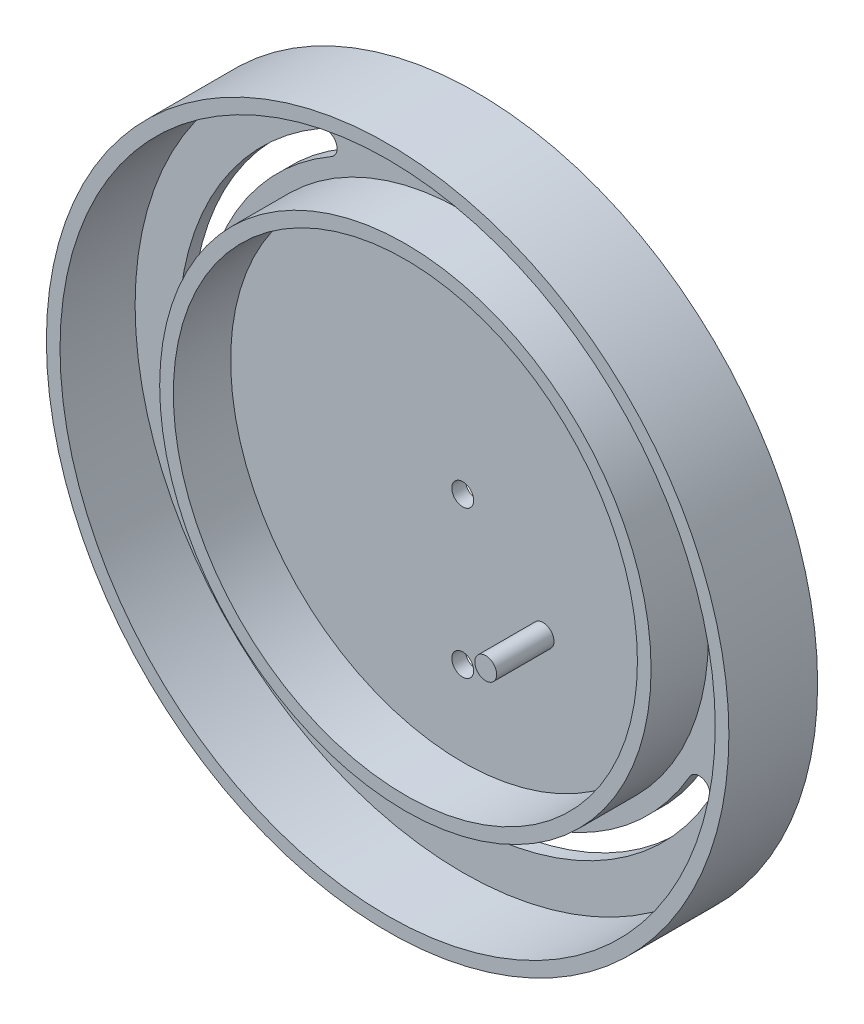
SolidWorks part; units mm, degrees
ref_plane "Front Plane" through (0, 0, 0) normal (0, 0, 1) x (1, 0, 0)
ref_plane "Top Plane" through (0, 0, 0) normal (0, 1, 0) x (1, 0, 0)
ref_plane "Right Plane" through (0, 0, 0) normal (1, 0, 0) x (0, 0, -1)
sketch "Sketch1" plane through (0, 0, 0) normal (0, 0, 1) x (1, 0, 0)
  line L0 (0, 0) -> (0, -27) construction
  circle A0 centre (0, 0) radius 36 construction
  circle A1 centre (0, 0) radius 60
  circle A2 centre (0, 0) radius 14 construction
  circle A3 centre (0, -27) radius 9 construction
  circle A4 centre (0, -27) radius 2
  circle A5 centre (14.7158, -14.9815) radius 10 construction
  circle A6 centre (14.7158, -14.9815) radius 7 construction
  circle A7 centre (14.7158, -14.9815) radius 2
  circle A8 centre (0, 0) radius 2
  circle A9 centre (0, 0) radius 50 construction
  arc A10 (0, 50) -> (50, 0) centre (0, 0) cw construction
  arc A11 (52, 0) -> (0, 52) centre (0, 0) ccw
  arc A12 (48, 0) -> (0, 48) centre (0, 0) ccw
  arc A13 (48, 0) -> (52, 0) centre (50, 0) ccw
  arc A14 (0, 52) -> (0, 48) centre (0, 50) ccw
  arc A15 (43.3013, -25) -> (-25, -43.3013) centre (0, 0) cw construction
  arc A16 (-26, -45.0333) -> (45.0333, -26) centre (0, 0) ccw
  arc A17 (-24, -41.5692) -> (41.5692, -24) centre (0, 0) ccw
  arc A18 (-24, -41.5692) -> (-26, -45.0333) centre (-25, -43.3013) ccw
  arc A19 (45.0333, -26) -> (41.5692, -24) centre (43.3013, -25) ccw
  arc A20 (-43.3013, -25) -> (-25, 43.3013) centre (0, 0) cw construction
  arc A21 (-26, 45.0333) -> (-45.0333, -26) centre (0, 0) ccw
  arc A22 (-24, 41.5692) -> (-41.5692, -24) centre (0, 0) ccw
  arc A23 (-24, 41.5692) -> (-26, 45.0333) centre (-25, 43.3013) ccw
  arc A24 (-45.0333, -26) -> (-41.5692, -24) centre (-43.3013, -25) ccw
  circle A25 centre (0, 0) radius 45
  circle A26 centre (0, 0) radius 42.5
  circle A27 centre (0, 0) radius 62.5
  point P16 (35.3553, 35.3553)
  point P25 (12.941, -48.2963)
  point P32 (-48.2963, 12.941)
  point P37 (0, 0)
  dimension "D1" = 72
  dimension "D2" = 120
  dimension "D3" = 28
  dimension "D4" = 4
  dimension "D5" = 18
  dimension "D6" = 20
  dimension "D7" = 14
  dimension "D8" = 4
  dimension "D9" = 4
  dimension "D10" = 100
  dimension "D11" = 4
  dimension "D13" = 2.5
  dimension "D14" = 85
  dimension "D15" = 2.5
  dimension "D12" = 3
extrude "Boss-Extrude1" add sketch "Sketch1" along normal blind 1.25 and the other way blind 1.25 contours A1 A25 A24 A21 A23 A22 A19 A16 A18 A17 A14 A11 A13 A12 | A26 A8 A7 A4 | A7 | A25 A26 region at (-58.3029, 0, 0) region at (14.7158, -14.9815, 0) region at (-43.7272, 0, 0) region at (-41.2979, 0, 0)
extrude "Boss-Extrude2" add sketch "Sketch1<3>" along normal blind 11.75 contours A7 | A25 | A26
sketch "Sketch1<3>" plane through (0, 0, 0) normal (0, 0, 1) x (1, 0, 0) same geometry as "Sketch1"
extrude "Boss-Extrude3" add sketch "Sketch1<4>" along normal blind 15 and the other way blind 1.25 contours A1 | A27
sketch "Sketch1<4>" plane through (0, 0, 0) normal (0, 0, 1) x (1, 0, 0) same geometry as "Sketch1"
